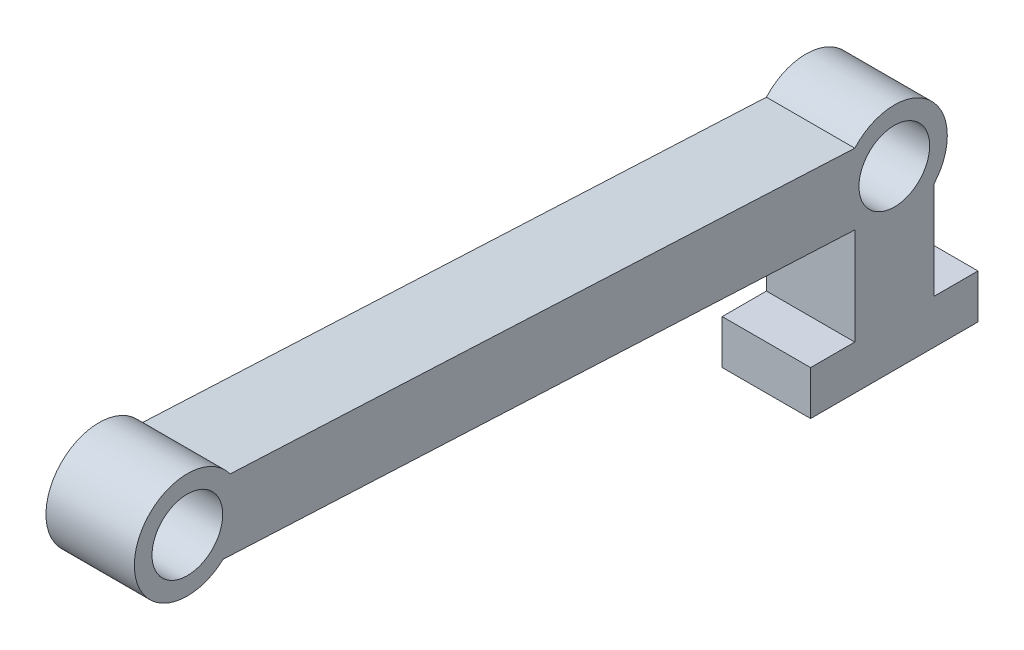
SolidWorks part; units mm, degrees
material "AISI 4340 Steel, annealed"
ref_plane "Front Plane" through (0, 0, 0) normal (0, 0, 1) x (1, 0, 0)
ref_plane "Top Plane" through (0, 0, 0) normal (0, 1, 0) x (1, 0, 0)
ref_plane "Right Plane" through (0, 0, 0) normal (1, 0, 0) x (0, 0, -1)
sketch "LinkFrame" plane through (0, 0, 0) normal (1, 0, 0) x (0, 0, -1)
  line L0 (-538.5321, -177.3158) -> (261.4679, -216.0436) construction
  line L1 (-490.1562, -141.8226) -> (216.7465, -176.0436)
  line L2 (-497.9804, -221.5375) -> (216.7465, -256.1372)
  line L5 (306.1892, -256.0436) -> (306.1892, -366.0436)
  line L7 (216.7465, -256.1372) -> (216.7465, -366.0436)
  line L8 (261.4679, -216.0436) -> (261.4679, -416.0436) construction
  line L9 (166.7465, -366.0436) -> (216.7465, -366.0436)
  line L10 (166.7465, -366.0436) -> (166.7465, -416.0436)
  line L11 (166.7465, -416.0436) -> (356.1892, -416.0436)
  line L12 (356.1892, -366.0436) -> (356.1892, -416.0436)
  line L13 (306.1892, -366.0436) -> (356.1892, -366.0436)
  arc A1 (306.1892, -256.0436) -> (216.7465, -176.0436) centre (261.4679, -216.0436) ccw
  arc A2 (-490.1562, -141.8226) -> (-497.9804, -221.5375) centre (-538.5321, -177.3158) ccw
  circle A5 centre (-538.5321, -177.3158) radius 40
  circle A6 centre (261.4679, -216.0436) radius 40
  point P8 (0, 0)
  point P12 (0, 0)
  dimension "D1" = 120
  dimension "D2" = 120
  dimension "D5" = 80
  dimension "D6" = 80
  dimension "D3" = 800
  dimension "D4" = 80
  dimension "D7" = 44.7214
  dimension "D8" = 44.7214
  dimension "D10" = 50
  dimension "D9" = 50
  dimension "D12" = 50
  dimension "D11" = 200
extrude "Boss-Extrude1" add sketch "LinkFrame" along normal blind 100
equation "\"D1@LinkFrame\" = 1.5 * \"HoleMountDiameter@PrintingPress.Assembly\""
equation "\"D2@LinkFrame\" = 1.5 * \"HoleMountDiameter@PrintingPress.Assembly\""
equation "\"LinkLength\" = 80cm"
equation "\"D3@LinkFrame\" = \"LinkLength\""
equation "\"D4@LinkFrame\" = \"HoleMountDiameter@PrintingPress.Assembly\""
equation "\"D5@LinkFrame\"=\"HoleMountDiameter@PrintingPress.Assembly\""
equation "\"D6@LinkFrame\"=\"HoleMountDiameter@PrintingPress.Assembly\""
equation "\"D1@Boss-Extrude1\"=\"RivetLength@PrintingPress.Assembly\""
equation "\"D10@LinkFrame\"=0.5*\"RivetLength@PrintingPress.Assembly\""
equation "\"D9@LinkFrame\"=0.5*\"RivetLength@PrintingPress.Assembly\""
equation "\"D12@LinkFrame\"=0.5*\"RivetLength@PrintingPress.Assembly\""
